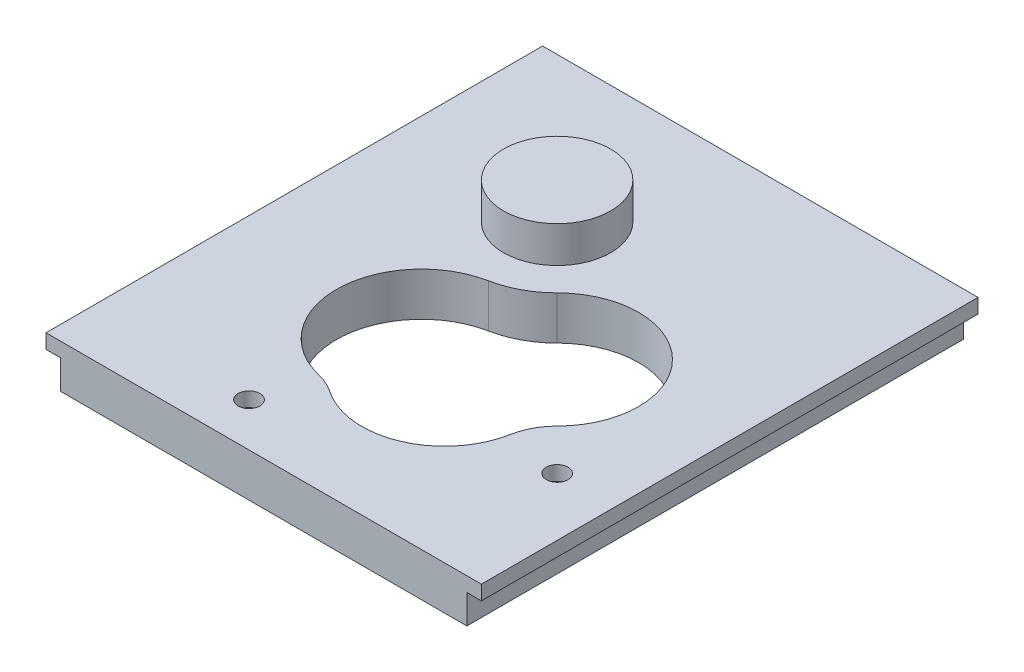
SolidWorks part; units mm, degrees
ref_plane "Front Plane" through (0, 0, 0) normal (0, 0, 1) x (1, 0, 0)
ref_plane "Top Plane" through (0, 0, 0) normal (0, 1, 0) x (1, 0, 0)
ref_plane "Right Plane" through (0, 0, 0) normal (1, 0, 0) x (0, 0, -1)
sketch "Sketch1" plane through (0, 0, 0) normal (0, 1, 0) x (1, 0, 0)
  line L0 (0, 0) -> (30.052, -30.052) construction
  line L1 (0, -42.5) -> (0, 0) construction
  line L3 (-20, 20) -> (36.052, 20)
  line L4 (-20, 20) -> (-20, -48.5)
  line L5 (-20, -48.5) -> (36.052, -48.5)
  line L6 (36.052, 20) -> (36.052, -48.5)
  circle A0 centre (0, 0) radius 7.39
  circle A1 centre (0, -42.5) radius 1.5
  circle A2 centre (30.052, -30.052) radius 1.5
  dimension "D3" = 3
  dimension "D4" = 3
  dimension "D5" = 14.78
  dimension "D1" = 42.5
  dimension "D2" = 42.5
  dimension "D6" = 45
  dimension "D7" = 6
  dimension "D8" = 6
  dimension "D9" = 20
  dimension "D10" = 20
extrude "Boss-Extrude1" add sketch "Sketch1" against normal blind 6 contours A0 | L6 L3 L4 L5 A2 A1 A0 region at (8.3758, 0, 14.8339) region at (0, 0, 0)
extrude "Boss-Extrude2" add sketch "Sketch1<3>" along normal blind 5 contours A0 region at (0, 0, 0)
sketch "Sketch1<3>" plane through (0, 0, 0) normal (0, 1, 0) x (1, 0, 0) same geometry as "Sketch1"
sketch "Sketch2" plane through (0, -6, 0) normal (0, -1, 0) x (1, 0, 0)
  circle A0 centre (0, 42.5) radius 1.95
  circle A1 centre (30.052, 30.052) radius 1.95
  circle M1 centre (30.052, 30.052) radius 1.5
  circle M2 centre (0, 42.5) radius 1.5
  dimension "D1" = 3.9
extrude "Cut-Extrude1" cut sketch "Sketch2" against normal blind 4 contours A0 M2 | A1 M1 region at (-1.8948, -6, 42.5) region at (28.1572, -6, 30.052)
sketch "Sketch3" plane through (0, 0, 48.5) normal (0, 0, 1) x (1, 0, 0)
  line L1 (-20, 0) -> (-22, 0)
  line L2 (-20, 0) -> (-20, -2)
  line L3 (-20, -2) -> (-22, -2)
  line L4 (-22, 0) -> (-22, -2)
  line L5 (36.052, 0) -> (38.052, 0)
  line L6 (36.052, 0) -> (36.052, -2)
  line L7 (36.052, -2) -> (38.052, -2)
  line L8 (38.052, 0) -> (38.052, -2)
  dimension "D1" = 2
  dimension "D2" = 2
extrude "Boss-Extrude3" add sketch "Sketch3" against normal up to surface (68.5 mm away) up to face at (8.026, -3, -20)
sketch "Sketch4" plane through (0, 0, 0) normal (0, 1, 0) x (1, 0, 0)
  arc A0 (8.4853, -8.4853) -> (2.3202, -11.7736) centre (0, 0) cw
  arc A1 (4.5347, -35.9093) -> (1.8601, -34.7193) centre (0, -42.5) ccw
  arc A2 (2.3202, -11.7736) -> (1.8601, -34.7193) centre (4.591, -23.2966) ccw
  arc A3 (22.1852, -28.5982) -> (24.3952, -24.3952) centre (30.052, -30.052) cw
  arc A4 (8.4853, -8.4853) -> (24.3952, -24.3952) centre (16.4402, -16.4402) cw
  arc A5 (22.1852, -28.5982) -> (4.5347, -35.9093) centre (10.9887, -26.5291) cw
  point P9 (-6.7101, -35.0778)
  point P15 (0, -10.595)
  point P17 (0, 0)
  point P18 (0, 0)
  point P19 (0, 0)
  point P20 (-8.9147, -19.4134)
  point P21 (0, 0)
  point P22 (22.8782, -23.5082)
  point P23 (1.8601, -11.7736)
  dimension "D1" = 8
  dimension "D2" = 8
  dimension "D3" = 12
extrude "Cut-Extrude2" cut sketch "Sketch4" against normal blind 10
